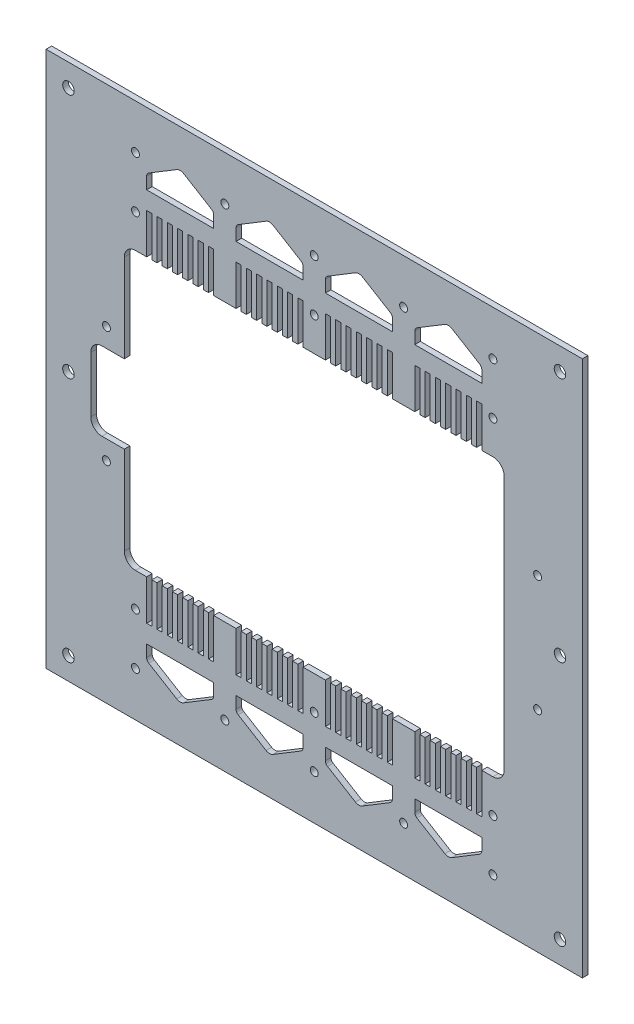
SolidWorks part; units mm, degrees
ref_plane "Front Plane" through (0, 0, 0) normal (0, 0, 1) x (1, 0, 0)
ref_plane "Top Plane" through (0, 0, 0) normal (0, 1, 0) x (1, 0, 0)
ref_plane "Right Plane" through (0, 0, 0) normal (1, 0, 0) x (0, 0, -1)
sketch "Sketch1" plane through (0, 0, 0) normal (0, 0, 1) x (1, 0, 0)
  line L0 (-152.4, 127) -> (-76.2, 127) construction
  line L1 (-152.4, 152.4) -> (152.4, 152.4)
  line L2 (-152.4, 152.4) -> (-152.4, -152.4)
  line L3 (-152.4, -152.4) -> (152.4, -152.4)
  line L4 (152.4, 152.4) -> (152.4, -152.4)
  line L5 (-76.2, 127) -> (-25.4, 127) construction
  line L6 (-25.4, 127) -> (25.4, 127) construction
  line L7 (25.4, 127) -> (76.2, 127) construction
  line L8 (76.2, 127) -> (152.4, 127) construction
  line L9 (-152.4, 0) -> (152.4, 0) construction
  line L10 (0, 152.4) -> (0, -152.4) construction
  line L11 (-118.11, 152.4) -> (-118.11, -152.4) construction
  line L12 (-152.4, -127) -> (152.4, -127) construction
  line L13 (127, 152.4) -> (127, -152.4) construction
  line L14 (-50.8, 152.4) -> (-50.8, -152.4) construction
  line L15 (50.8, 152.4) -> (50.8, -152.4) construction
  line L16 (-101.6, 152.4) -> (-101.6, -152.4) construction
  line L17 (-95.25, 66.04) -> (-57.15, 66.04) construction
  line L18 (-95.25, 66.04) -> (-95.25, -66.04) construction
  line L19 (-95.25, -66.04) -> (-57.15, -66.04) construction
  line L20 (-57.15, 66.04) -> (-57.15, -66.04) construction
  line L21 (-44.45, 66.04) -> (-6.35, 66.04) construction
  line L22 (-44.45, 66.04) -> (-44.45, -66.04) construction
  line L23 (-44.45, -66.04) -> (-6.35, -66.04) construction
  line L24 (-6.35, 66.04) -> (-6.35, -66.04) construction
  line L25 (6.35, 66.04) -> (44.45, 66.04) construction
  line L26 (6.35, 66.04) -> (6.35, -66.04) construction
  line L27 (6.35, -66.04) -> (44.45, -66.04) construction
  line L28 (44.45, 66.04) -> (44.45, -66.04) construction
  line L29 (57.15, 66.04) -> (95.25, 66.04) construction
  line L30 (57.15, 66.04) -> (57.15, -66.04) construction
  line L31 (57.15, -66.04) -> (95.25, -66.04) construction
  line L32 (95.25, 66.04) -> (95.25, -66.04) construction
  line L33 (101.6, 152.4) -> (101.6, -152.4) construction
  line L34 (-152.4, 120.65) -> (152.4, 120.65) construction
  line L35 (-101.6, 39.7057) -> (-95.25, 39.7057) construction
  line L36 (-57.15, 39.7057) -> (-50.8, 39.7057) construction
  line L37 (-76.2, 66.04) -> (-76.2, 0) construction
  line L38 (-76.2, 0) -> (-76.2, -66.04) construction
  line L39 (-152.4, 72.39) -> (152.4, 72.39) construction
  line L40 (-152.4, -72.39) -> (152.4, -72.39) construction
  line L41 (-76.2, 66.04) -> (-76.2, 72.39) construction
  line L42 (-95.25, -66.04) -> (-95.25, -72.39) construction
  line L43 (95.25, 39.7057) -> (101.6, 39.7057) construction
  line L44 (-95.25, 111.76) -> (-57.15, 111.76)
  line L45 (-57.15, 111.76) -> (-57.15, 118.4779)
  line L46 (-94.0266, 120.65) -> (-78.1749, 130.2582)
  line L47 (-95.25, 111.76) -> (-95.25, 118.4779)
  line L48 (-58.3734, 120.65) -> (-74.2251, 130.2582)
  line L49 (-107.3169, 130.81) -> (-83.1894, 130.81) construction
  line L50 (-6.35, 111.76) -> (-6.35, 118.4779)
  line L51 (-7.5734, 120.65) -> (-23.4251, 130.2582)
  line L52 (-43.2266, 120.65) -> (-27.3749, 130.2582)
  line L53 (-44.45, 111.76) -> (-44.45, 118.4779)
  line L54 (-6.35, 111.76) -> (-44.45, 111.76)
  line L55 (44.45, 111.76) -> (44.45, 118.4779)
  line L56 (43.2266, 120.65) -> (27.3749, 130.2582)
  line L57 (7.5734, 120.65) -> (23.4251, 130.2582)
  line L58 (6.35, 111.76) -> (6.35, 118.4779)
  line L59 (6.35, 111.76) -> (44.45, 111.76)
  line L60 (95.25, 111.76) -> (57.15, 111.76)
  line L61 (95.25, 111.76) -> (95.25, 118.4779)
  line L62 (94.0266, 120.65) -> (78.1749, 130.2582)
  line L63 (58.3734, 120.65) -> (74.2251, 130.2582)
  line L64 (57.15, 111.76) -> (57.15, 118.4779)
  line L65 (-95.25, -111.76) -> (-95.25, -118.4779)
  line L66 (-94.0266, -120.65) -> (-78.1749, -130.2582)
  line L67 (-58.3734, -120.65) -> (-74.2251, -130.2582)
  line L68 (-95.25, -111.76) -> (-57.15, -111.76)
  line L69 (-57.15, -111.76) -> (-57.15, -118.4779)
  line L70 (-44.45, -111.76) -> (-44.45, -118.4779)
  line L71 (-43.2266, -120.65) -> (-27.3749, -130.2582)
  line L72 (-6.35, -111.76) -> (-44.45, -111.76)
  line L73 (-7.5734, -120.65) -> (-23.4251, -130.2582)
  line L74 (-6.35, -111.76) -> (-6.35, -118.4779)
  line L75 (6.35, -111.76) -> (6.35, -118.4779)
  line L76 (7.5734, -120.65) -> (23.4251, -130.2582)
  line L77 (43.2266, -120.65) -> (27.3749, -130.2582)
  line L78 (6.35, -111.76) -> (44.45, -111.76)
  line L79 (44.45, -111.76) -> (44.45, -118.4779)
  line L80 (57.15, -111.76) -> (57.15, -118.4779)
  line L81 (58.3734, -120.65) -> (74.2251, -130.2582)
  line L82 (94.0266, -120.65) -> (78.1749, -130.2582)
  line L83 (95.25, -111.76) -> (57.15, -111.76)
  line L84 (95.25, -111.76) -> (95.25, -118.4779)
  line L85 (-152.4, 97.79) -> (152.4, 97.79) construction
  line L86 (-50.8, 39.7057) -> (-44.45, 39.7057) construction
  line L87 (-127, 152.4) -> (-127, -152.4) construction
  line L89 (-95.25, 101.6) -> (-92.3192, 101.6)
  line L90 (-95.25, 101.6) -> (-95.25, -101.6)
  line L96 (-90.8538, 101.6) -> (-90.8538, 68.58) construction
  line L97 (-89.3885, 101.6) -> (-89.3885, 68.58)
  line L98 (-92.3192, 101.6) -> (-92.3192, 68.58)
  line L99 (-83.5269, 101.6) -> (-83.5269, 68.58)
  line L100 (-86.4577, 101.6) -> (-86.4577, 68.58)
  line L101 (-89.3885, 101.6) -> (-86.4577, 101.6)
  line L102 (-77.6654, 101.6) -> (-77.6654, 68.58)
  line L103 (-80.5962, 101.6) -> (-80.5962, 68.58)
  line L104 (-83.5269, 101.6) -> (-80.5962, 101.6)
  line L105 (-71.8038, 101.6) -> (-71.8038, 68.58)
  line L106 (-74.7346, 101.6) -> (-74.7346, 68.58)
  line L107 (-77.6654, 101.6) -> (-74.7346, 101.6)
  line L108 (-65.9423, 101.6) -> (-65.9423, 68.58)
  line L109 (-68.8731, 101.6) -> (-68.8731, 68.58)
  line L110 (-71.8038, 101.6) -> (-68.8731, 101.6)
  line L111 (-60.0808, 101.6) -> (-60.0808, 68.58)
  line L112 (-63.0115, 101.6) -> (-63.0115, 68.58)
  line L113 (-65.9423, 101.6) -> (-63.0115, 101.6)
  line L114 (-57.15, -101.6) -> (-57.15, 101.6)
  line L115 (-60.0808, 101.6) -> (-57.15, 101.6)
  line L116 (-92.3192, 68.58) -> (-89.3885, 68.58) construction
  line L117 (-60.0808, -101.6) -> (-57.15, -101.6)
  line L118 (-60.0808, -101.6) -> (-60.0808, -68.58)
  line L119 (-63.0115, -101.6) -> (-63.0115, -68.58)
  line L120 (-65.9423, -101.6) -> (-65.9423, -68.58)
  line L121 (-65.9423, -101.6) -> (-63.0115, -101.6)
  line L122 (-68.8731, -101.6) -> (-68.8731, -68.58)
  line L123 (-71.8038, -101.6) -> (-68.8731, -101.6)
  line L124 (-71.8038, -101.6) -> (-71.8038, -68.58)
  line L125 (-74.7346, -101.6) -> (-74.7346, -68.58)
  line L126 (-77.6654, -101.6) -> (-74.7346, -101.6)
  line L127 (-77.6654, -101.6) -> (-77.6654, -68.58)
  line L128 (-80.5962, -101.6) -> (-80.5962, -68.58)
  line L129 (-83.5269, -101.6) -> (-80.5962, -101.6)
  line L130 (-83.5269, -101.6) -> (-83.5269, -68.58)
  line L131 (-86.4577, -101.6) -> (-86.4577, -68.58)
  line L132 (-89.3885, -101.6) -> (-86.4577, -101.6)
  line L133 (-89.3885, -101.6) -> (-89.3885, -68.58)
  line L134 (-92.3192, -101.6) -> (-92.3192, -68.58)
  line L135 (-95.25, -101.6) -> (-92.3192, -101.6)
  line L136 (-9.2808, 68.58) -> (-12.2115, 68.58) construction
  line L137 (6.35, 66.04) -> (44.45, 66.04) construction
  line L138 (-6.35, -66.04) -> (-6.35, -72.39) construction
  line L139 (-25.4, 66.04) -> (-25.4, 72.39) construction
  line L140 (-25.4, 0) -> (-25.4, -66.04) construction
  line L141 (-25.4, 66.04) -> (-25.4, 0) construction
  line L142 (-44.45, 66.04) -> (-44.45, -66.04) construction
  line L143 (-6.35, -66.04) -> (-44.45, -66.04) construction
  line L144 (-6.35, 66.04) -> (-6.35, -66.04) construction
  line L145 (-6.35, 66.04) -> (-44.45, 66.04) construction
  line L146 (-6.35, -101.6) -> (-9.2808, -101.6)
  line L147 (-9.2808, -101.6) -> (-9.2808, -68.58)
  line L148 (-12.2115, -101.6) -> (-12.2115, -68.58)
  line L149 (-12.2115, -101.6) -> (-15.1423, -101.6)
  line L150 (-15.1423, -101.6) -> (-15.1423, -68.58)
  line L151 (-18.0731, -101.6) -> (-18.0731, -68.58)
  line L152 (-18.0731, -101.6) -> (-21.0038, -101.6)
  line L153 (-21.0038, -101.6) -> (-21.0038, -68.58)
  line L154 (-23.9346, -101.6) -> (-23.9346, -68.58)
  line L155 (-23.9346, -101.6) -> (-26.8654, -101.6)
  line L156 (-26.8654, -101.6) -> (-26.8654, -68.58)
  line L157 (-29.7962, -101.6) -> (-29.7962, -68.58)
  line L158 (-29.7962, -101.6) -> (-32.7269, -101.6)
  line L159 (-32.7269, -101.6) -> (-32.7269, -68.58)
  line L160 (-35.6577, -101.6) -> (-38.5885, -101.6)
  line L161 (-35.6577, -101.6) -> (-35.6577, -68.58)
  line L162 (-38.5885, -101.6) -> (-38.5885, -68.58)
  line L163 (-41.5192, -101.6) -> (-41.5192, -68.58)
  line L164 (-41.5192, -101.6) -> (-44.45, -101.6)
  line L165 (-41.5192, 101.6) -> (-44.45, 101.6)
  line L166 (-44.45, -101.6) -> (-44.45, 101.6)
  line L167 (-35.6577, 101.6) -> (-38.5885, 101.6)
  line L168 (-38.5885, 101.6) -> (-38.5885, 68.58)
  line L169 (-41.5192, 101.6) -> (-41.5192, 68.58)
  line L170 (-29.7962, 101.6) -> (-32.7269, 101.6)
  line L171 (-32.7269, 101.6) -> (-32.7269, 68.58)
  line L172 (-35.6577, 101.6) -> (-35.6577, 68.58)
  line L173 (-23.9346, 101.6) -> (-26.8654, 101.6)
  line L174 (-26.8654, 101.6) -> (-26.8654, 68.58)
  line L175 (-29.7962, 101.6) -> (-29.7962, 68.58)
  line L176 (-18.0731, 101.6) -> (-21.0038, 101.6)
  line L177 (-21.0038, 101.6) -> (-21.0038, 68.58)
  line L178 (-23.9346, 101.6) -> (-23.9346, 68.58)
  line L179 (-12.2115, 101.6) -> (-15.1423, 101.6)
  line L180 (-15.1423, 101.6) -> (-15.1423, 68.58)
  line L181 (-18.0731, 101.6) -> (-18.0731, 68.58)
  line L182 (-9.2808, 101.6) -> (-9.2808, 68.58)
  line L183 (-12.2115, 101.6) -> (-12.2115, 68.58)
  line L184 (-6.35, 101.6) -> (-6.35, -101.6)
  line L185 (-6.35, 101.6) -> (-9.2808, 101.6)
  line L186 (6.35, 66.04) -> (6.35, -66.04) construction
  line L187 (6.35, -66.04) -> (44.45, -66.04) construction
  line L188 (44.45, 66.04) -> (44.45, -66.04) construction
  line L189 (25.4, 66.04) -> (25.4, 0) construction
  line L190 (25.4, 0) -> (25.4, -66.04) construction
  line L191 (25.4, 66.04) -> (25.4, 72.39) construction
  line L192 (6.35, -66.04) -> (6.35, -72.39) construction
  line L193 (9.2808, 68.58) -> (12.2115, 68.58) construction
  line L194 (6.35, 66.04) -> (6.35, -66.04) construction
  line L195 (44.45, -66.04) -> (6.35, -66.04) construction
  line L196 (44.45, 66.04) -> (44.45, -66.04) construction
  line L197 (44.45, 66.04) -> (6.35, 66.04) construction
  line L198 (6.35, 101.6) -> (9.2808, 101.6)
  line L199 (6.35, 101.6) -> (6.35, -101.6)
  line L200 (12.2115, 101.6) -> (12.2115, 68.58)
  line L201 (9.2808, 101.6) -> (9.2808, 68.58)
  line L202 (18.0731, 101.6) -> (18.0731, 68.58)
  line L203 (15.1423, 101.6) -> (15.1423, 68.58)
  line L204 (12.2115, 101.6) -> (15.1423, 101.6)
  line L205 (23.9346, 101.6) -> (23.9346, 68.58)
  line L206 (21.0038, 101.6) -> (21.0038, 68.58)
  line L207 (18.0731, 101.6) -> (21.0038, 101.6)
  line L208 (29.7962, 101.6) -> (29.7962, 68.58)
  line L209 (26.8654, 101.6) -> (26.8654, 68.58)
  line L210 (23.9346, 101.6) -> (26.8654, 101.6)
  line L211 (35.6577, 101.6) -> (35.6577, 68.58)
  line L212 (32.7269, 101.6) -> (32.7269, 68.58)
  line L213 (29.7962, 101.6) -> (32.7269, 101.6)
  line L214 (41.5192, 101.6) -> (41.5192, 68.58)
  line L215 (38.5885, 101.6) -> (38.5885, 68.58)
  line L216 (35.6577, 101.6) -> (38.5885, 101.6)
  line L217 (44.45, -101.6) -> (44.45, 101.6)
  line L218 (41.5192, 101.6) -> (44.45, 101.6)
  line L219 (41.5192, -101.6) -> (44.45, -101.6)
  line L220 (41.5192, -101.6) -> (41.5192, -68.58)
  line L221 (38.5885, -101.6) -> (38.5885, -68.58)
  line L222 (35.6577, -101.6) -> (35.6577, -68.58)
  line L223 (35.6577, -101.6) -> (38.5885, -101.6)
  line L224 (32.7269, -101.6) -> (32.7269, -68.58)
  line L225 (29.7962, -101.6) -> (32.7269, -101.6)
  line L226 (29.7962, -101.6) -> (29.7962, -68.58)
  line L227 (26.8654, -101.6) -> (26.8654, -68.58)
  line L228 (23.9346, -101.6) -> (26.8654, -101.6)
  line L229 (23.9346, -101.6) -> (23.9346, -68.58)
  line L230 (21.0038, -101.6) -> (21.0038, -68.58)
  line L231 (18.0731, -101.6) -> (21.0038, -101.6)
  line L232 (18.0731, -101.6) -> (18.0731, -68.58)
  line L233 (15.1423, -101.6) -> (15.1423, -68.58)
  line L234 (12.2115, -101.6) -> (15.1423, -101.6)
  line L235 (12.2115, -101.6) -> (12.2115, -68.58)
  line L236 (9.2808, -101.6) -> (9.2808, -68.58)
  line L237 (6.35, -101.6) -> (9.2808, -101.6)
  line L238 (57.15, 66.04) -> (95.25, 66.04) construction
  line L239 (57.15, 66.04) -> (57.15, -66.04) construction
  line L240 (57.15, -66.04) -> (95.25, -66.04) construction
  line L241 (95.25, 66.04) -> (95.25, -66.04) construction
  line L242 (92.3192, 68.58) -> (89.3885, 68.58) construction
  line L243 (95.25, -66.04) -> (95.25, -72.39) construction
  line L244 (76.2, 66.04) -> (76.2, 72.39) construction
  line L245 (76.2, 0) -> (76.2, -66.04) construction
  line L246 (76.2, 66.04) -> (76.2, 0) construction
  line L247 (57.15, 66.04) -> (57.15, -66.04) construction
  line L248 (95.25, -66.04) -> (57.15, -66.04) construction
  line L249 (95.25, 66.04) -> (95.25, -66.04) construction
  line L250 (95.25, 66.04) -> (57.15, 66.04) construction
  line L251 (57.15, 66.04) -> (57.15, -66.04) construction
  line L252 (95.25, -66.04) -> (57.15, -66.04) construction
  line L253 (95.25, 66.04) -> (95.25, -66.04) construction
  line L254 (95.25, 66.04) -> (57.15, 66.04) construction
  line L255 (95.25, -101.6) -> (92.3192, -101.6)
  line L256 (92.3192, -101.6) -> (92.3192, -68.58)
  line L257 (89.3885, -101.6) -> (89.3885, -68.58)
  line L258 (89.3885, -101.6) -> (86.4577, -101.6)
  line L259 (86.4577, -101.6) -> (86.4577, -68.58)
  line L260 (83.5269, -101.6) -> (83.5269, -68.58)
  line L261 (83.5269, -101.6) -> (80.5962, -101.6)
  line L262 (80.5962, -101.6) -> (80.5962, -68.58)
  line L263 (77.6654, -101.6) -> (77.6654, -68.58)
  line L264 (77.6654, -101.6) -> (74.7346, -101.6)
  line L265 (74.7346, -101.6) -> (74.7346, -68.58)
  line L266 (71.8038, -101.6) -> (71.8038, -68.58)
  line L267 (71.8038, -101.6) -> (68.8731, -101.6)
  line L268 (68.8731, -101.6) -> (68.8731, -68.58)
  line L269 (65.9423, -101.6) -> (63.0115, -101.6)
  line L270 (65.9423, -101.6) -> (65.9423, -68.58)
  line L271 (63.0115, -101.6) -> (63.0115, -68.58)
  line L272 (60.0808, -101.6) -> (60.0808, -68.58)
  line L273 (60.0808, -101.6) -> (57.15, -101.6)
  line L274 (60.0808, 101.6) -> (57.15, 101.6)
  line L275 (57.15, -101.6) -> (57.15, 101.6)
  line L276 (65.9423, 101.6) -> (63.0115, 101.6)
  line L277 (63.0115, 101.6) -> (63.0115, 68.58)
  line L278 (60.0808, 101.6) -> (60.0808, 68.58)
  line L279 (71.8038, 101.6) -> (68.8731, 101.6)
  line L280 (68.8731, 101.6) -> (68.8731, 68.58)
  line L281 (65.9423, 101.6) -> (65.9423, 68.58)
  line L282 (77.6654, 101.6) -> (74.7346, 101.6)
  line L283 (74.7346, 101.6) -> (74.7346, 68.58)
  line L284 (71.8038, 101.6) -> (71.8038, 68.58)
  line L285 (83.5269, 101.6) -> (80.5962, 101.6)
  line L286 (80.5962, 101.6) -> (80.5962, 68.58)
  line L287 (77.6654, 101.6) -> (77.6654, 68.58)
  line L288 (89.3885, 101.6) -> (86.4577, 101.6)
  line L289 (86.4577, 101.6) -> (86.4577, 68.58)
  line L290 (83.5269, 101.6) -> (83.5269, 68.58)
  line L291 (92.3192, 101.6) -> (92.3192, 68.58)
  line L292 (89.3885, 101.6) -> (89.3885, 68.58)
  line L293 (95.25, 101.6) -> (95.25, -101.6)
  line L294 (95.25, 101.6) -> (92.3192, 101.6)
  line L295 (-101.6, 39.7057) -> (-107.95, 39.7057) construction
  line L296 (-101.6, 78.74) -> (101.6, 78.74)
  line L297 (-107.95, 72.39) -> (-107.95, -72.39)
  line L298 (-101.6, -78.74) -> (101.6, -78.74)
  line L299 (107.95, 72.39) -> (107.95, -72.39)
  line L300 (-97.0611, 78.74) -> (-97.0611, 72.39) construction
  line L301 (-107.95, 22.225) -> (-120.65, 22.225)
  line L302 (-127, 15.875) -> (-127, -15.875)
  line L303 (-120.65, -22.225) -> (-107.95, -22.225)
  circle A0 centre (-76.2, 127) radius 3.3655
  circle A1 centre (-25.4, 127) radius 3.3655
  circle A2 centre (25.4, 127) radius 3.3655
  circle A3 centre (76.2, 127) radius 3.3655
  circle A4 centre (-101.6, 0) radius 2.2479
  circle A5 centre (-50.8, 0) radius 2.2479
  circle A6 centre (0, 0) radius 2.2479
  circle A7 centre (101.6, 0) radius 2.2479
  circle A8 centre (50.8, 0) radius 2.2479
  circle A9 centre (-50.8, 127) radius 2.2479
  circle A10 centre (0, 127) radius 2.2479
  circle A11 centre (50.8, 127) radius 2.2479
  circle A12 centre (-101.6, 72.39) radius 2.2479
  circle A13 centre (0, 72.39) radius 2.2479
  circle A14 centre (101.6, 72.39) radius 2.2479
  circle A15 centre (-101.6, -72.39) radius 2.2479
  circle A16 centre (0, -72.39) radius 2.2479
  circle A17 centre (101.6, -72.39) radius 2.2479
  arc A18 (-74.2251, 130.2582) -> (-78.1749, 130.2582) centre (-76.2, 127) ccw
  arc A19 (-57.15, 118.4779) -> (-58.3734, 120.65) centre (-59.69, 118.4779) ccw
  arc A20 (-95.25, 118.4779) -> (-94.0266, 120.65) centre (-92.71, 118.4779) cw
  arc A21 (-6.35, 118.4779) -> (-7.5734, 120.65) centre (-8.89, 118.4779) ccw
  arc A22 (-27.3749, 130.2582) -> (-23.4251, 130.2582) centre (-25.4, 127) cw
  arc A23 (-44.45, 118.4779) -> (-43.2266, 120.65) centre (-41.91, 118.4779) cw
  arc A24 (44.45, 118.4779) -> (43.2266, 120.65) centre (41.91, 118.4779) ccw
  arc A25 (27.3749, 130.2582) -> (23.4251, 130.2582) centre (25.4, 127) ccw
  arc A26 (6.35, 118.4779) -> (7.5734, 120.65) centre (8.89, 118.4779) cw
  arc A27 (95.25, 118.4779) -> (94.0266, 120.65) centre (92.71, 118.4779) ccw
  arc A28 (74.2251, 130.2582) -> (78.1749, 130.2582) centre (76.2, 127) cw
  arc A29 (57.15, 118.4779) -> (58.3734, 120.65) centre (59.69, 118.4779) cw
  circle A30 centre (-76.2, -127) radius 3.3655
  circle A31 centre (-25.4, -127) radius 3.3655
  circle A32 centre (25.4, -127) radius 3.3655
  circle A33 centre (76.2, -127) radius 3.3655
  arc A34 (-95.25, -118.4779) -> (-94.0266, -120.65) centre (-92.71, -118.4779) ccw
  arc A35 (-74.2251, -130.2582) -> (-78.1749, -130.2582) centre (-76.2, -127) cw
  arc A36 (-57.15, -118.4779) -> (-58.3734, -120.65) centre (-59.69, -118.4779) cw
  arc A37 (-44.45, -118.4779) -> (-43.2266, -120.65) centre (-41.91, -118.4779) ccw
  arc A38 (-27.3749, -130.2582) -> (-23.4251, -130.2582) centre (-25.4, -127) ccw
  arc A39 (-6.35, -118.4779) -> (-7.5734, -120.65) centre (-8.89, -118.4779) cw
  arc A40 (6.35, -118.4779) -> (7.5734, -120.65) centre (8.89, -118.4779) ccw
  arc A41 (27.3749, -130.2582) -> (23.4251, -130.2582) centre (25.4, -127) cw
  arc A42 (44.45, -118.4779) -> (43.2266, -120.65) centre (41.91, -118.4779) cw
  arc A43 (57.15, -118.4779) -> (58.3734, -120.65) centre (59.69, -118.4779) ccw
  arc A44 (74.2251, -130.2582) -> (78.1749, -130.2582) centre (76.2, -127) ccw
  arc A45 (95.25, -118.4779) -> (94.0266, -120.65) centre (92.71, -118.4779) cw
  circle A46 centre (50.8, -127) radius 2.2479
  circle A47 centre (0, -127) radius 2.2479
  circle A48 centre (-50.8, -127) radius 2.2479
  circle A49 centre (-101.6, 97.79) radius 2.2479
  circle A50 centre (0, 97.79) radius 2.2479
  circle A51 centre (101.6, 97.79) radius 2.2479
  circle A52 centre (101.6, 127) radius 2.2479
  circle A53 centre (-101.6, 127) radius 2.2479
  circle A54 centre (-118.11, 33.02) radius 2.2479
  circle A55 centre (127, 33.02) radius 2.2479
  circle A56 centre (-101.6, -127) radius 2.2479
  circle A57 centre (101.6, -127) radius 2.2479
  circle A58 centre (101.6, -97.79) radius 2.2479
  circle A59 centre (0, -97.79) radius 2.2479
  circle A60 centre (-101.6, -97.79) radius 2.2479
  circle A61 centre (-118.11, -33.02) radius 2.2479
  circle A62 centre (127, -33.02) radius 2.2479
  circle A63 centre (-139.7, 139.7) radius 3.2639
  circle A64 centre (-139.7, 0) radius 3.2639
  circle A65 centre (-139.7, -139.7) radius 3.2639
  circle A66 centre (139.7, -139.7) radius 3.2639
  circle A67 centre (139.7, 0) radius 3.2639
  circle A68 centre (139.7, 139.7) radius 3.2639
  arc A70 (-92.3192, 68.58) -> (-89.3885, 68.58) centre (-90.8538, 68.58) ccw
  arc A71 (-86.4577, 68.58) -> (-83.5269, 68.58) centre (-84.9923, 68.58) ccw
  arc A72 (-80.5962, 68.58) -> (-77.6654, 68.58) centre (-79.1308, 68.58) ccw
  arc A73 (-74.7346, 68.58) -> (-71.8038, 68.58) centre (-73.2692, 68.58) ccw
  arc A74 (-68.8731, 68.58) -> (-65.9423, 68.58) centre (-67.4077, 68.58) ccw
  arc A75 (-63.0115, 68.58) -> (-60.0808, 68.58) centre (-61.5462, 68.58) ccw
  arc A76 (-63.0115, -68.58) -> (-60.0808, -68.58) centre (-61.5462, -68.58) cw
  arc A77 (-68.8731, -68.58) -> (-65.9423, -68.58) centre (-67.4077, -68.58) cw
  arc A78 (-74.7346, -68.58) -> (-71.8038, -68.58) centre (-73.2692, -68.58) cw
  arc A79 (-80.5962, -68.58) -> (-77.6654, -68.58) centre (-79.1308, -68.58) cw
  arc A80 (-86.4577, -68.58) -> (-83.5269, -68.58) centre (-84.9923, -68.58) cw
  arc A81 (-92.3192, -68.58) -> (-89.3885, -68.58) centre (-90.8538, -68.58) cw
  arc A82 (-9.2808, -68.58) -> (-12.2115, -68.58) centre (-10.7462, -68.58) ccw
  arc A83 (-15.1423, -68.58) -> (-18.0731, -68.58) centre (-16.6077, -68.58) ccw
  arc A84 (-21.0038, -68.58) -> (-23.9346, -68.58) centre (-22.4692, -68.58) ccw
  arc A85 (-26.8654, -68.58) -> (-29.7962, -68.58) centre (-28.3308, -68.58) ccw
  arc A86 (-32.7269, -68.58) -> (-35.6577, -68.58) centre (-34.1923, -68.58) ccw
  arc A87 (-38.5885, -68.58) -> (-41.5192, -68.58) centre (-40.0538, -68.58) ccw
  arc A88 (-38.5885, 68.58) -> (-41.5192, 68.58) centre (-40.0538, 68.58) cw
  arc A89 (-32.7269, 68.58) -> (-35.6577, 68.58) centre (-34.1923, 68.58) cw
  arc A90 (-26.8654, 68.58) -> (-29.7962, 68.58) centre (-28.3308, 68.58) cw
  arc A91 (-21.0038, 68.58) -> (-23.9346, 68.58) centre (-22.4692, 68.58) cw
  arc A92 (-15.1423, 68.58) -> (-18.0731, 68.58) centre (-16.6077, 68.58) cw
  arc A93 (-9.2808, 68.58) -> (-12.2115, 68.58) centre (-10.7462, 68.58) cw
  arc A94 (9.2808, 68.58) -> (12.2115, 68.58) centre (10.7462, 68.58) ccw
  arc A95 (15.1423, 68.58) -> (18.0731, 68.58) centre (16.6077, 68.58) ccw
  arc A96 (21.0038, 68.58) -> (23.9346, 68.58) centre (22.4692, 68.58) ccw
  arc A97 (26.8654, 68.58) -> (29.7962, 68.58) centre (28.3308, 68.58) ccw
  arc A98 (32.7269, 68.58) -> (35.6577, 68.58) centre (34.1923, 68.58) ccw
  arc A99 (38.5885, 68.58) -> (41.5192, 68.58) centre (40.0538, 68.58) ccw
  arc A100 (38.5885, -68.58) -> (41.5192, -68.58) centre (40.0538, -68.58) cw
  arc A101 (32.7269, -68.58) -> (35.6577, -68.58) centre (34.1923, -68.58) cw
  arc A102 (26.8654, -68.58) -> (29.7962, -68.58) centre (28.3308, -68.58) cw
  arc A103 (21.0038, -68.58) -> (23.9346, -68.58) centre (22.4692, -68.58) cw
  arc A104 (15.1423, -68.58) -> (18.0731, -68.58) centre (16.6077, -68.58) cw
  arc A105 (9.2808, -68.58) -> (12.2115, -68.58) centre (10.7462, -68.58) cw
  arc A106 (92.3192, -68.58) -> (89.3885, -68.58) centre (90.8538, -68.58) ccw
  arc A107 (86.4577, -68.58) -> (83.5269, -68.58) centre (84.9923, -68.58) ccw
  arc A108 (80.5962, -68.58) -> (77.6654, -68.58) centre (79.1308, -68.58) ccw
  arc A109 (74.7346, -68.58) -> (71.8038, -68.58) centre (73.2692, -68.58) ccw
  arc A110 (68.8731, -68.58) -> (65.9423, -68.58) centre (67.4077, -68.58) ccw
  arc A111 (63.0115, -68.58) -> (60.0808, -68.58) centre (61.5462, -68.58) ccw
  arc A112 (63.0115, 68.58) -> (60.0808, 68.58) centre (61.5462, 68.58) cw
  arc A113 (68.8731, 68.58) -> (65.9423, 68.58) centre (67.4077, 68.58) cw
  arc A114 (74.7346, 68.58) -> (71.8038, 68.58) centre (73.2692, 68.58) cw
  arc A115 (80.5962, 68.58) -> (77.6654, 68.58) centre (79.1308, 68.58) cw
  arc A116 (86.4577, 68.58) -> (83.5269, 68.58) centre (84.9923, 68.58) cw
  arc A117 (92.3192, 68.58) -> (89.3885, 68.58) centre (90.8538, 68.58) cw
  arc A118 (-101.6, 78.74) -> (-107.95, 72.39) centre (-101.6, 72.39) ccw
  arc A119 (-107.95, -72.39) -> (-101.6, -78.74) centre (-101.6, -72.39) ccw
  arc A120 (101.6, 78.74) -> (107.95, 72.39) centre (101.6, 72.39) cw
  arc A121 (101.6, -78.74) -> (107.95, -72.39) centre (101.6, -72.39) ccw
  arc A122 (-127, -15.875) -> (-120.65, -22.225) centre (-120.65, -15.875) ccw
  arc A123 (-120.65, 22.225) -> (-127, 15.875) centre (-120.65, 15.875) ccw
  point P10 (-76.2, 111.76)
  point P63 (50.8, 127)
  point P95 (-76.2, 66.04)
  point P97 (-25.4, 66.04)
  point P99 (25.4, 66.04)
  point P101 (76.2, 66.04)
  point P116 (-95.25, 0)
  point P118 (-44.45, 0)
  point P119 (6.35, 0)
  point P120 (57.15, 0)
  point P219 (-76.2, 33.02)
  point P259 (0, 78.74)
  point P260 (-107.95, 0)
  point P545 (-127, 0)
  point P548 (-127, -22.225)
  point P551 (-127, 22.225)
  dimension "D1" = 6.731
  dimension "D7" = 4.4958
  dimension "D11" = 7.62
  dimension "D13" = 2.54
  dimension "D19" = 6.5278
  dimension "D25" = 6.35
  dimension "D26" = 6.35
  dimension "D27" = 6.35
  dimension "D29" = 6.35
  dimension "D2" = 25.4
  dimension "D3" = 50.8
  dimension "D4" = 25.4
  dimension "D5" = 25.4
  dimension "D6" = 25.4
  dimension "D8" = 38.1
  dimension "D9" = 31.75
  dimension "D10" = 132.08
  dimension "D12" = 19.05
  dimension "D14" = 25.4
  dimension "D15" = 304.8
  dimension "D16" = 304.8
  dimension "D17" = 8.89
  dimension "D18" = 12.7
  dimension "D20" = 12.7
  dimension "D21" = 12.7
  dimension "D23" = 33.02
  dimension "D24" = 10.16
  dimension "D28" = 44.45
  dimension "D22" = 6
extrude "Boss-Extrude1" add sketch "Sketch1" along normal blind 3.175 contours L4 L1 L2 L3 A67 A62 A60 A58 A56 A55 A54 A53 A52 A51 A50 A49 A47 L84 A45 L82 A44 L81 A43 L80 L83 L74 A39 L73 A38 L71 A37 L70 L72 L64 A29 region at (0, 148.0895, 0)
